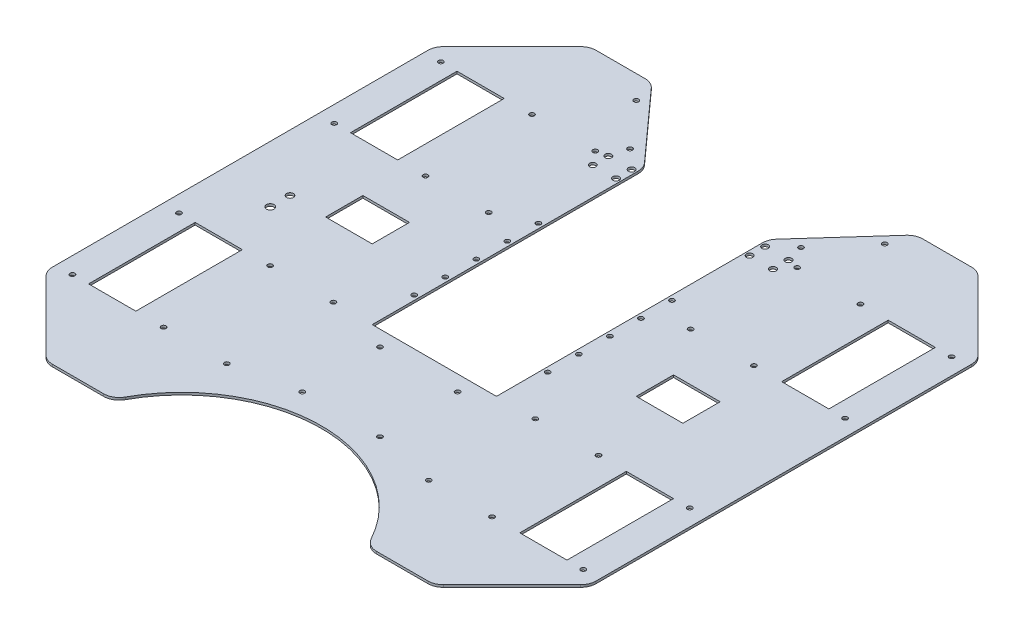
SolidWorks part; units mm, degrees
material "PMMA"
ref_plane "前视基准面" through (0, 0, 0) normal (0, 0, 1) x (1, 0, 0)
ref_plane "上视基准面" through (0, 0, 0) normal (0, 1, 0) x (1, 0, 0)
ref_plane "右视基准面" through (0, 0, 0) normal (1, 0, 0) x (0, 0, -1)
other "Configuration Table"
sketch "草图1" plane through (0, 0, 0) normal (0, 1, 0) x (1, 0, 0)
  line L0 (-125, 175) -> (-175, 125)
  line L1 (125, -175) -> (81.7103, -175)
  line L2 (175, -125) -> (175, 125)
  line L3 (125, 175) -> (85, 175)
  line L4 (-175, -125) -> (-175, 125)
  line L5 (-85, 175) -> (-40, 125)
  line L7 (125, 175) -> (175, 125)
  line L8 (175, -125) -> (125, -175)
  line L9 (-125, -175) -> (-175, -125)
  line L10 (40, 125) -> (85, 175)
  line L11 (-85, 175) -> (-125, 175)
  line L12 (40, 125) -> (40, 85)
  line L13 (40, 85) -> (-40, 85)
  line L14 (-40, 85) -> (-40, 125)
  line L15 (-153.994, 50) -> (-123.594, 50)
  line L16 (-123.594, 50) -> (-123.594, 118.58)
  line L17 (-123.594, 118.58) -> (-153.994, 118.58)
  line L18 (-153.994, 118.58) -> (-153.994, 50)
  line L19 (123.594, 50) -> (153.994, 50)
  line L20 (153.994, 50) -> (153.994, 118.58)
  line L21 (153.994, 118.58) -> (123.594, 118.58)
  line L22 (123.594, 118.58) -> (123.594, 50)
  line L23 (-175, 0) -> (175, 0) construction
  line L24 (-123.594, -118.58) -> (-153.994, -118.58)
  line L25 (-123.594, -50) -> (-123.594, -118.58)
  line L26 (-153.994, -50) -> (-123.594, -50)
  line L27 (-153.994, -118.58) -> (-153.994, -50)
  line L28 (153.994, -118.58) -> (123.594, -118.58)
  line L29 (153.994, -50) -> (153.994, -118.58)
  line L30 (123.594, -50) -> (153.994, -50)
  line L31 (123.594, -118.58) -> (123.594, -50)
  line L32 (-81.7103, -175) -> (-125, -175)
  line L33 (-80, 160) -> (-55, 131) construction
  line L34 (0, 85) -> (0, -124.4881) construction
  line L35 (-40, 85) -> (-40, -25)
  line L36 (-40, -25) -> (40, -25)
  line L37 (40, -25) -> (40, 85)
  circle A0 centre (-55, 131) radius 1.55
  circle A1 centre (-80, 160) radius 1.55
  circle A2 centre (55, 131) radius 1.55
  circle A3 centre (80, 160) radius 1.55
  circle A4 centre (-65, 118.58) radius 1.55
  circle A5 centre (-65, 50) radius 1.55
  circle A6 centre (-105.72, 50) radius 1.55
  circle A7 centre (-105.72, 118.58) radius 1.55
  circle A12 centre (-164.434, 118.58) radius 1.55
  circle A13 centre (-164.434, 50) radius 1.55
  circle A14 centre (-65, -118.58) radius 1.55
  circle A15 centre (-65, -50) radius 1.55
  circle A16 centre (-105.72, -50) radius 1.55
  circle A17 centre (-105.72, -118.58) radius 1.55
  circle A18 centre (-164.434, -50) radius 1.55
  circle A19 centre (-164.434, -118.58) radius 1.55
  circle A20 centre (65, 50) radius 1.55
  circle A21 centre (105.72, 50) radius 1.55
  circle A22 centre (105.72, 118.58) radius 1.55
  circle A23 centre (65, 118.58) radius 1.55
  circle A24 centre (164.434, 118.58) radius 1.55
  circle A25 centre (164.434, 50) radius 1.55
  circle A26 centre (164.434, -118.58) radius 1.55
  circle A27 centre (164.434, -50) radius 1.55
  circle A28 centre (105.72, -50) radius 1.55
  circle A29 centre (105.72, -118.58) radius 1.55
  circle A30 centre (65, -118.58) radius 1.55
  circle A31 centre (65, -50) radius 1.55
  arc A32 (-81.7103, -175) -> (81.7103, -175) centre (0, -212.7283) cw
  circle A33 centre (25, -60) radius 1.55
  circle A34 centre (25, -110) radius 1.55
  circle A35 centre (-25, -60) radius 1.55
  circle A36 centre (-25, -110) radius 1.55
  circle A37 centre (-43, 120) radius 2.05
  circle A38 centre (-43, 110) radius 2.05
  circle A39 centre (-58, 110) radius 2.05
  circle A40 centre (-58, 120) radius 2.05
  circle A41 centre (43, 120) radius 2.05
  circle A42 centre (58, 120) radius 2.05
  circle A43 centre (58, 110) radius 2.05
  circle A44 centre (43, 110) radius 2.05
  circle A45 centre (43, -20) radius 1.55
  circle A46 centre (43, 0) radius 1.55
  circle A47 centre (43, 20) radius 1.55
  circle A48 centre (43, 40) radius 1.55
  circle A49 centre (43, 60) radius 1.55
  circle A50 centre (-43, -20) radius 1.55
  circle A51 centre (-43, 0) radius 1.55
  circle A52 centre (-43, 20) radius 1.55
  circle A53 centre (-43, 40) radius 1.55
  circle A54 centre (-43, 60) radius 1.55
  circle A55 centre (-138.4729, -4.4575) radius 2.205
  circle A56 centre (-138.4729, -17.1575) radius 2.5
  point P0 (0, 0)
  point P1 (-85, 175)
  point P2 (85, 175)
  point P3 (40, 125)
  point P4 (-40, 125)
  point P6 (125, 175)
  point P8 (175, 125)
  point P10 (175, -125)
  point P11 (125, -175)
  point P12 (-125, -175)
  point P13 (-175, -125)
  point P24 (-80, 160)
  point P25 (-55, 131)
  point P26 (55, 131)
  point P27 (80, 160)
  point P36 (-164.434, 118.58)
  point P37 (-164.434, 50)
  point P38 (-153.994, 118.58)
  point P39 (-123.594, 50)
  point P40 (-105.72, 118.58)
  point P41 (-105.72, 50)
  point P42 (-65, 118.58)
  point P43 (-65, 50)
  point P47 (-123.594, 118.58)
  point P53 (-153.994, 50)
  point P66 (-40, 85)
  point P67 (40, 85)
  point P70 (105.72, 50)
  point P71 (65, 50)
  point P72 (123.594, 50)
  point P73 (153.994, 50)
  point P74 (164.434, 50)
  point P75 (65, 118.58)
  point P76 (105.72, 118.58)
  point P77 (123.594, 118.58)
  point P78 (153.994, 118.58)
  point P81 (164.434, 118.58)
  point P85 (-65, -118.58)
  point P88 (-65, -50)
  point P91 (-105.72, -50)
  point P94 (-105.72, -118.58)
  point P101 (-164.434, -50)
  point P104 (-164.434, -118.58)
  point P118 (164.434, -118.58)
  point P121 (164.434, -50)
  point P128 (105.72, -50)
  point P131 (105.72, -118.58)
  point P134 (65, -118.58)
  point P137 (65, -50)
  point P157 (58, 110)
  point P158 (43, 110)
  point P159 (43, 120)
  point P160 (58, 120)
  point P189 (-43, 60)
  point P198 (0, 0)
  point P199 (0, 0)
  point P200 (0, 0)
  point P201 (0, 0)
  point P202 (0, 0)
  point P203 (0, 0)
  point P204 (0, 0)
  dimension "D29" = 3.1
  dimension "D30" = 3.1
  dimension "D31" = 3.1
  dimension "D32" = 3.1
  dimension "D40" = 3.1
  dimension "D41" = 3.1
  dimension "D42" = 3.1
  dimension "D43" = 3.1
  dimension "D44" = 3.1
  dimension "D45" = 3.1
  dimension "D46" = 3.1
  dimension "D47" = 3.1
  dimension "D48" = 3.1
  dimension "D49" = 3.1
  dimension "D60" = 3.1
  dimension "D61" = 3.1
  dimension "D62" = 43.2897
  dimension "D63" = 90
  dimension "D67" = 3.1
  dimension "D68" = 3.1
  dimension "D69" = 3.1
  dimension "D70" = 3.1
  dimension "D75" = 4.1
  dimension "D76" = 4.1
  dimension "D77" = 4.1
  dimension "D78" = 4.1
  dimension "D80" = 110
  dimension "D83" = 5
  dimension "D85" = 20
  dimension "D89" = 4.41
  dimension "D90" = 5
  dimension "D1" = 175
  dimension "D2" = 175
  dimension "D3" = 125
  dimension "D4" = 125
  dimension "D5" = 125
  dimension "D6" = 125
  dimension "D7" = 125
  dimension "D8" = 125
  dimension "D9" = 125
  dimension "D10" = 125
  dimension "D11" = 175
  dimension "D12" = 175
  dimension "D13" = 40
  dimension "D14" = 40
  dimension "D15" = 85
  dimension "D16" = 85
  dimension "D17" = 125
  dimension "D18" = 125
  dimension "D19" = 40
  dimension "D20" = 45
  dimension "D21" = 160
  dimension "D22" = 160
  dimension "D23" = 80
  dimension "D24" = 80
  dimension "D25" = 55
  dimension "D26" = 131
  dimension "D27" = 55
  dimension "D28" = 131
  dimension "D33" = 50
  dimension "D34" = 118.58
  dimension "D35" = 65
  dimension "D38" = 30.4
  dimension "D39" = 10.44
  dimension "D50" = 40
  dimension "D51" = 40
  dimension "D52" = 85
  dimension "D53" = 85
  dimension "D54" = 138.013
  dimension "D55" = 65
  dimension "D58" = 30.4
  dimension "D59" = 10.44
  dimension "D64" = 0
  dimension "D65" = 25
  dimension "D66" = 25
  dimension "D71" = 60
  dimension "D72" = 50
  dimension "D73" = 15
  dimension "D74" = 10
  dimension "D79" = 43
  dimension "D81" = 120
  dimension "D82" = 110
  dimension "D84" = 3
  dimension "D86" = 20
  dimension "D87" = 20
  dimension "D88" = 20
  dimension "D91" = 12.7
extrude "凸台-拉伸1" add sketch "草图1" along normal blind 1.5 contours A55 | A56 | A1 | A0 | L8 L1 A32 L32 L9 L4 L0 L11 L5 L14 L13 L12 L10 L3 L7 L2 | A5 | A3 | A2 | A4 | A7 | A12 | L16 L17 L18 L15 | A6 | L21 L22 L19 L20 | A13 | A16 | A17 | A14 | A15 | A18 | A19 | L25 L24 L27 L26 | A20 | A21 | A22 | A23 | A24 | A25 | A28 | A26 | A27 | L28 L31 L30 L29 | A30 | A31 | A29 | A35 | A36 | A33 | A34 | A39 | A40 | A37 | A38 | A43 | A42 | A41 | A44 region at (-138.4729, 0, 4.4575) region at (-138.4729, 0, 17.1575)
fillet "圆角1" radius 10 1 edges at (-40, 0.75, -125)
fillet "圆角2" radius 10 1 edges at (40, 0.75, -125)
fillet "圆角3" radius 10 12 edges at (-85, 0.75, -175) (85, 0.75, -175) (125, 0.75, -175) (175, 0.75, -125) (175, 0.75, 125) (125, 0.75, 175) (81.7103, 0.75, 175) (-81.7103, 0.75, 175) (-125, 0.75, 175) (-175, 0.75, 125) (-175, 0.75, -125) (-125, 0.75, -175)
sketch "草图2" plane through (0, 1.5, 0) normal (0, 1, 0) x (1, 0, 0)
  line L1 (-40, 85) -> (40, 85)
  line L2 (-40, 85) -> (-40, -50)
  line L3 (-40, -50) -> (40, -50)
  line L4 (40, 85) -> (40, -50)
  dimension "D1" = 80
  dimension "D2" = 135
extrude "切除-拉伸1" cut sketch "草图2" against normal blind 10
sketch "草图3" plane through (0, 1.5, 0) normal (0, 1, 0) x (1, 0, 0)
  line L0 (-87.875, -175) -> (-120.8579, -175) construction
  line L1 (-115, 19) -> (-85, 19)
  line L2 (-115, 19) -> (-115, -5)
  line L3 (-115, -5) -> (-85, -5)
  line L4 (-85, 19) -> (-85, -5)
  line L5 (-175, -120.8579) -> (-175, 120.8579) construction
  line L6 (120.8579, -175) -> (87.875, -175) construction
  line L7 (85, 19) -> (115, 19)
  line L8 (85, 19) -> (85, -5)
  line L9 (85, -5) -> (115, -5)
  line L10 (115, 19) -> (115, -5)
  line L11 (175, -120.8579) -> (175, 120.8579) construction
  dimension "D1" = 30
  dimension "D2" = 24
  dimension "D3" = 170
  dimension "D4" = 60
  dimension "D5" = 30
  dimension "D6" = 24
  dimension "D7" = 170
  dimension "D8" = 60
extrude "切除-拉伸2" cut sketch "草图3" against normal blind 10
extrude "切除-拉伸3" cut sketch "草图1<4>" along normal blind 10 contours A54 | A53 | A52 | A51 | A50 | A49 | A48 | A47 | A46 | A45
sketch "草图1<4>" plane through (0, 0, 0) normal (0, 1, 0) x (1, 0, 0) same geometry as "草图1"
